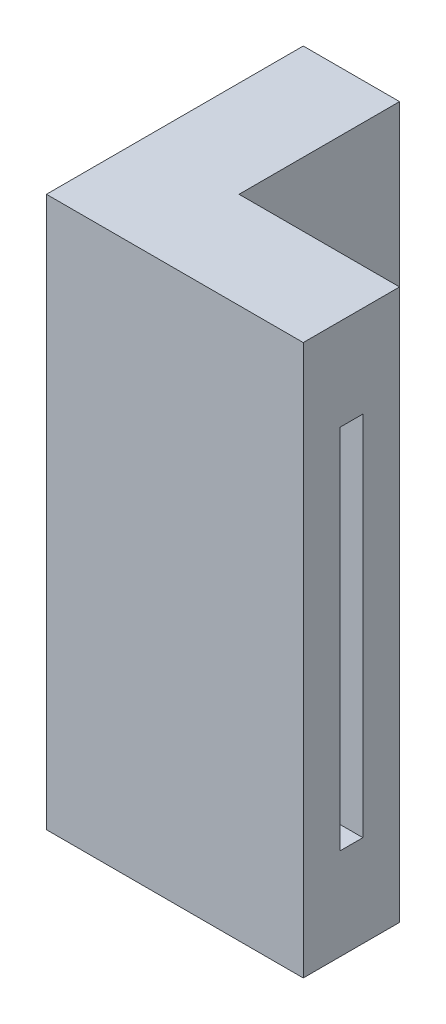
SolidWorks part; units mm, degrees
ref_plane "Front" through (0, 0, 0) normal (0, 0, 1) x (1, 0, 0)
ref_plane "Top" through (0, 0, 0) normal (0, 1, 0) x (1, 0, 0)
ref_plane "Right" through (0, 0, 0) normal (1, 0, 0) x (0, 0, -1)
sketch "Sketch1" plane through (0, 0, 0) normal (0, 1, 0) x (1, 0, 0)
  line L0 (0, 0) -> (0, 25.4)
  line L1 (0, -23.9493) -> (0, 23.9493) construction
  line L3 (3.175, 25.4) -> (3.175, 3.175)
  line L4 (0, 0) -> (25.4, 0)
  line L5 (-55, 0) -> (55, 0) construction
  line L7 (25.4, 3.175) -> (3.175, 3.175)
  line L8 (8.255, 30.48) -> (8.255, 8.255)
  line L9 (30.48, 8.255) -> (8.255, 8.255)
  line L10 (30.48, -5.08) -> (30.48, 8.255)
  line L11 (-5.08, -5.08) -> (30.48, -5.08)
  line L12 (-5.08, -5.08) -> (-5.08, 30.48)
  line L13 (-5.08, 30.48) -> (8.255, 30.48)
  line L14 (25.4, 3.175) -> (30.48, 3.175)
  line L15 (30.48, 3.175) -> (30.48, 0)
  line L16 (30.48, 0) -> (25.4, 0)
  line L17 (3.175, 25.4) -> (3.175, 30.48)
  line L18 (25.4, 0) -> (25.4, 3.175) construction
  line L19 (3.175, 30.48) -> (0, 30.48)
  line L20 (0, 30.48) -> (0, 25.4)
  line L22 (0, 25.4) -> (3.175, 25.4) construction
  dimension "D1" = 25.4
  dimension "D2" = 3.175
  dimension "D3" = 25.4
  dimension "D4" = 3.175
  dimension "D5" = 5.08
extrude "Boss-Extrude2" add sketch "Sketch1" along normal blind 76.2 contours L20 L13 L12 L11 L10 L16 L4 L0 | L17 L3 L7 L14 L10 L9 L8 L13 region at (12.7, 0, 0.5029) region at (5.715, 0, -30.0938)
extrude "Boss-Extrude3" add sketch "Sketch1<5>" along normal blind 12.7 contours L13 L20 L0 L4 L16 L10 L14 L7 L3 L17 region at (0.4311, 0, -12.7)
sketch "Sketch1<5>" plane through (0, 0, 0) normal (0, 1, 0) x (1, 0, 0) same geometry as "Sketch1"
sketch "Sketch2" plane through (0, 76.2, 0) normal (0, 1, 0) x (1, 0, 0)
  line L0 (3.175, 30.48) -> (3.175, 3.175) construction
  line L1 (3.175, 3.175) -> (30.48, 3.175) construction
  line L2 (30.48, 3.175) -> (30.48, 8.255) construction
  line L3 (30.48, 8.255) -> (8.255, 8.255) construction
  line L4 (8.255, 8.255) -> (8.255, 30.48) construction
  line L5 (8.255, 30.48) -> (3.175, 30.48) construction
  line L6 (0, 0) -> (0, 30.48)
  line L7 (0, 30.48) -> (-5.08, 30.48)
  line L8 (-5.08, 30.48) -> (-5.08, -5.08)
  line L9 (-5.08, -5.08) -> (30.48, -5.08)
  line L10 (30.48, -5.08) -> (30.48, 0)
  line L11 (30.48, 0) -> (0, 0)
  line L12 (0, 0) -> (0, 30.48)
  line L13 (0, 30.48) -> (-5.08, 30.48)
  line L14 (-5.08, 30.48) -> (-5.08, -5.08)
  line L15 (-5.08, -5.08) -> (30.48, -5.08)
  line L16 (30.48, -5.08) -> (30.48, 0)
  line L17 (30.48, 0) -> (0, 0)
  line L18 (3.175, 30.48) -> (0, 30.48) construction
  line L19 (0, 30.48) -> (0, 0) construction
  line L20 (0, 0) -> (30.48, 0) construction
  line L21 (30.48, 0) -> (30.48, 3.175) construction
  line L22 (30.48, 3.175) -> (3.175, 3.175) construction
  line L23 (3.175, 3.175) -> (3.175, 30.48) construction
  line L24 (3.175, 30.48) -> (3.175, 3.175)
  line L25 (3.175, 3.175) -> (30.48, 3.175)
  line L26 (30.48, 3.175) -> (30.48, 8.255)
  line L27 (30.48, 8.255) -> (8.255, 8.255)
  line L28 (8.255, 8.255) -> (8.255, 30.48)
  line L29 (8.255, 30.48) -> (3.175, 30.48)
  line L30 (3.175, 30.48) -> (0, 30.48)
  line L31 (0, 30.48) -> (0, 0)
  line L32 (0, 0) -> (30.48, 0)
  line L33 (30.48, 0) -> (30.48, 3.175)
  line L34 (30.48, 3.175) -> (3.175, 3.175)
  line L35 (3.175, 3.175) -> (3.175, 30.48)
  line M7 (0, 0) -> (0, 30.48)
  line M8 (0, 30.48) -> (-5.08, 30.48)
  line M9 (-5.08, 30.48) -> (-5.08, -5.08)
  line M10 (-5.08, -5.08) -> (30.48, -5.08)
  line M11 (30.48, -5.08) -> (30.48, 0)
  line M12 (30.48, 0) -> (0, 0)
  dimension "D1" = 0
extrude "Boss-Extrude4" add sketch "Sketch2" against normal blind 12.7 contours L28 L29 L24 L25 L26 L27 | L33 L25 L24 L30 M12 M7 | M12 M7 M8 M9 M10 M11 region at (15.24, 76.2, 0.5029) region at (0.4311, 76.2, -15.24) region at (5.715, 76.2, -30.0938)
sketch "Sketch3" plane through (0, 0, 0) normal (0, -1, 0) x (1, 0, 0)
  line L6 (8.255, -8.255) -> (30.48, -8.255)
  line L7 (30.48, -8.255) -> (30.48, 5.08)
  line L8 (30.48, 5.08) -> (-5.08, 5.08)
  line L9 (-5.08, 5.08) -> (-5.08, -30.48)
  line L10 (-5.08, -30.48) -> (8.255, -30.48)
  line L11 (8.255, -30.48) -> (8.255, -8.255)
  line L12 (8.255, -8.255) -> (30.48, -8.255)
  line L13 (30.48, -8.255) -> (30.48, 5.08)
  line L14 (30.48, 5.08) -> (-5.08, 5.08)
  line L15 (-5.08, 5.08) -> (-5.08, -30.48)
  line L16 (-5.08, -30.48) -> (8.255, -30.48)
  line L17 (8.255, -30.48) -> (8.255, -8.255)
  circle A0 centre (1.5875, -19.3675) radius 2.1
  circle A1 centre (19.3675, -1.5875) radius 2.1
  dimension "D2" = 4.2
  dimension "D3" = 4.2
  dimension "D1" = 0
extrude "Cut-Extrude1" cut sketch "Sketch3" against normal blind 6.35 contours A1 | A0 region at (1.5875, 0, -19.3675) region at (19.3675, 0, -1.5875)
